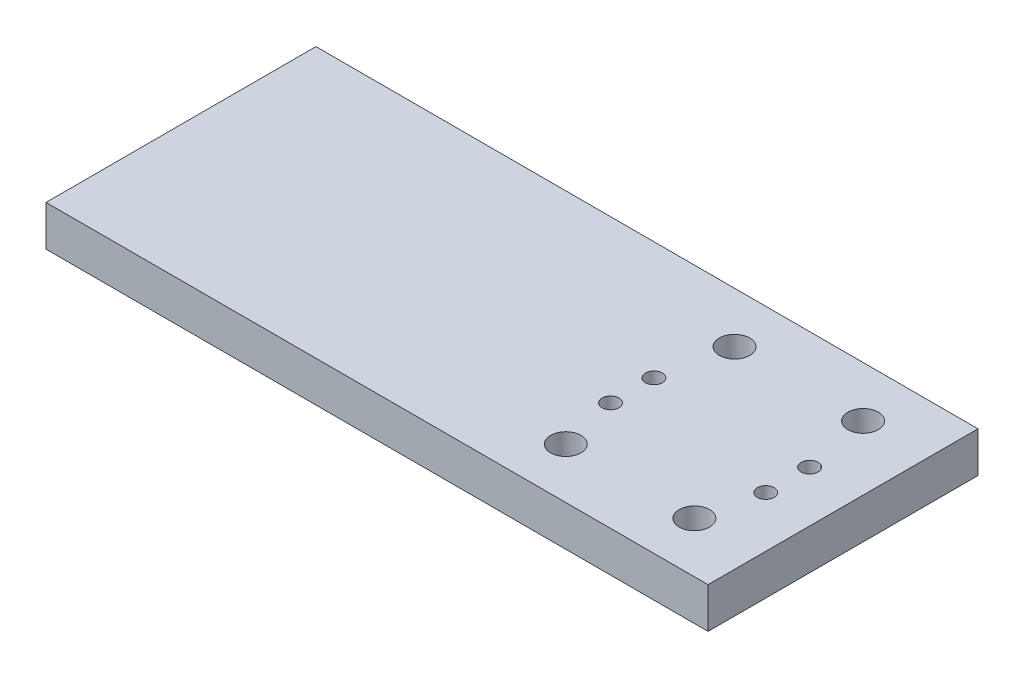
SolidWorks part; units mm, degrees
ref_plane "Front Plane" through (0, 0, 0) normal (0, 0, 1) x (1, 0, 0)
ref_plane "Top Plane" through (0, 0, 0) normal (0, 1, 0) x (1, 0, 0)
ref_plane "Right Plane" through (0, 0, 0) normal (1, 0, 0) x (0, 0, -1)
sketch "Sketch1" plane through (0, 0, 0) normal (0, 1, 0) x (1, 0, 0)
  line L1 (-38.1, 40) -> (38.1, 40)
  line L2 (-38.1, 40) -> (-38.1, -40)
  line L3 (-38.1, -40) -> (38.1, -40)
  line L4 (38.1, 40) -> (38.1, -40)
  line L5 (-38.1, 40) -> (38.1, -40) construction
  line L6 (-38.1, -40) -> (38.1, 40) construction
  circle A0 centre (19.05, 25) radius 4.5
  circle A1 centre (-19.05, 25) radius 4.5
  circle A2 centre (-19.05, -25) radius 4.5
  circle A3 centre (19.05, -25) radius 4.5
  point P0 (0, 0)
  dimension "D1" = 80
  dimension "D2" = 76.2
extrude "Boss-Extrude1" add sketch "Sketch1" along normal blind 12
sketch "Sketch2" plane through (0, 12, 0) normal (0, 1, 0) x (1, 0, 0)
  line L1 (-158.1, -40) -> (-158.1, 40)
  line L2 (-158.1, 40) -> (-38.1, 40)
  line L3 (-158.1, -40) -> (-38.1, -40)
  line L4 (-38.1, -40) -> (-38.1, 40)
extrude "Boss-Extrude2" add sketch "Sketch2" against normal up to surface (12 mm away) up to face at (0, 0, 0)
sketch "Sketch3" plane through (0, 12, 0) normal (0, 1, 0) x (1, 0, 0)
  circle A0 centre (-23, -7.8005) radius 2.5
  circle A1 centre (-23, 5.0516) radius 2.5
  circle A2 centre (23, 5.1995) radius 2.5
  circle A3 centre (23, -7.8005) radius 2.5
extrude "Cut-Extrude1" cut sketch "Sketch3" against normal through all
